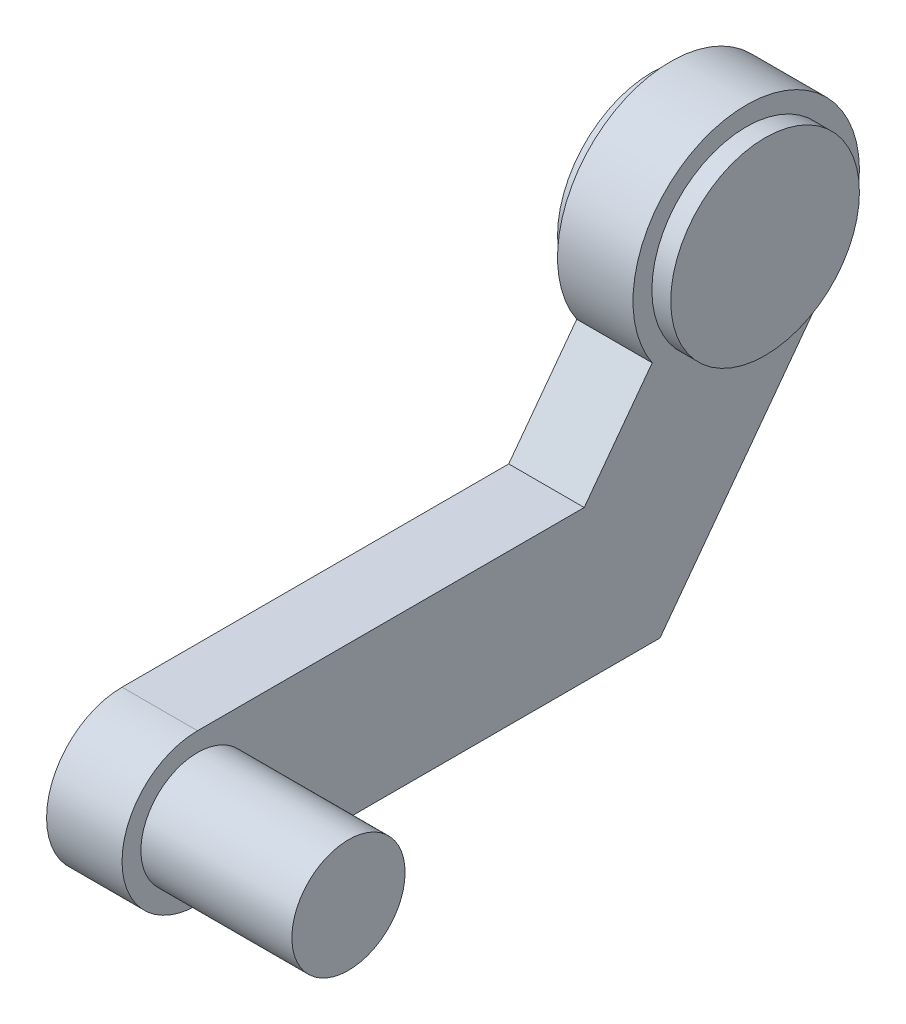
SolidWorks part; units mm, degrees
material "AISI 1045 Steel, cold drawn"
ref_plane "Front Plane" through (0, 0, 0) normal (1, 0, 0) x (0, 1, 0)
ref_plane "Top Plane" through (0, 0, 0) normal (0, 0, 1) x (0, 1, 0)
ref_plane "Right Plane" through (0, 0, 0) normal (0, 1, 0) x (-1, 0, 0)
sketch "Sketch1" plane through (0, 0, 0) normal (1, 0, 0) x (0, 1, 0)
  line L0 (0, 25.9949) -> (0, -26.3039) construction
  line L1 (-44.2064, 0) -> (41.2779, 0) construction
  line L2 (-16.18, 29.08) -> (-16.18, 4.57)
  line L3 (-16.18, 4.57) -> (-3.5841, -4.8119)
  line L4 (-16.18, 4.57) -> (-31.5374, 16.0087) construction
  line L5 (-16.18, 4.57) -> (-16.18, 2.7234) construction
  line L6 (-8.18, 29.08) -> (-8.18, 8.5866)
  line L7 (-8.18, 8.5866) -> (-3.342, 4.9831)
  line L9 (-8.18, 29.08) -> (-8.18, 4.57) construction
  line L10 (-11.4012, 10.9858) -> (1.1947, 1.604) construction
  circle A0 centre (0, 0) radius 6
  circle A1 centre (0, 0) radius 5
  circle A2 centre (-12.18, 29.08) radius 4
  circle A3 centre (-12.18, 29.08) radius 3
  dimension "D1" = 10
  dimension "D2" = 12
  dimension "D3" = 8
  dimension "D4" = 6
  dimension "D5" = 29.08
  dimension "D6" = 12.18
  dimension "D7" = 126.68
  dimension "D8" = 8
extrude "Boss-Extrude1" add sketch "Sketch1" along normal mid plane 4 contours A2 L2 L3 A0 L7 L6 | A2 A3 | A0 A1 region at (0, -11.3014, 12.295) region at (0, -12.18, 32.9669) region at (0, -5.8285, 0.144)
extrude "Boss-Extrude2" add sketch "Sketch1<3>" along normal mid plane 6 contours A1
sketch "Sketch1<3>" plane through (0, 0, 0) normal (1, 0, 0) x (0, 1, 0) same geometry as "Sketch1"
extrude "Boss-Extrude3" add sketch "Sketch1<4>" along normal blind 12 from surface contours A3 starting at face at (-2, -7.6975, 12.5423)
sketch "Sketch1<4>" plane through (0, 0, 0) normal (1, 0, 0) x (0, 1, 0) same geometry as "Sketch1"
